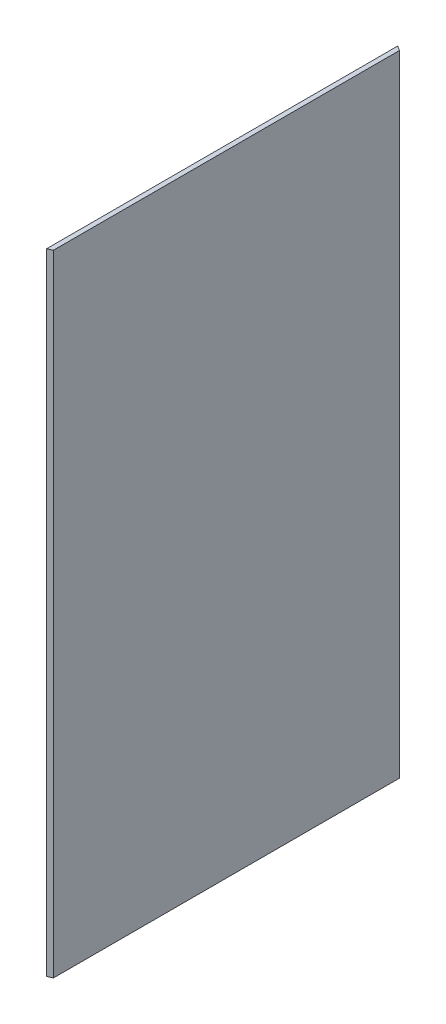
SolidWorks part; units mm, degrees
ref_plane "Спереди" through (0, 0, 0) normal (0, 0, 1) x (1, 0, 0)
ref_plane "Сверху" through (0, 0, 0) normal (0, 1, 0) x (1, 0, 0)
ref_plane "Справа" through (0, 0, 0) normal (1, 0, 0) x (0, 0, -1)
sketch "Эскиз1" plane through (0, 0, 0) normal (0, 1, 0) x (1, 0, 0)
  line L0 (4.0186, 1.7475) -> (79.181, -66.868) construction
  line L1 (0, 0) -> (4, 1.7645)
  line L2 (0, 0) -> (0, 297.3876)
  line L3 (0, 297.3876) -> (4, 294.8273)
  line L4 (4, 1.7645) -> (4, 294.8273)
  dimension "D1" = 4
extrude "Вытянуть1" add sketch "Эскиз1" along normal up to surface (533.7137 mm away)
sketch "Эскиз2" plane through (0, 0, 0) normal (-1, 0, 0) x (0, 0, 1)
  line L0 (-272.3275, 260.902) -> (-272.3275, -22.3628)
  line L1 (-272.3275, 260.902) -> (-25.1909, 260.902)
  line L3 (-272.3275, -22.3628) -> (-25.1909, -22.3628)
  line L4 (-25.1909, 260.902) -> (-25.1909, -22.3628)
  line L6 (-264.3275, 152.3571) -> (-192.5685, 152.3571) construction
